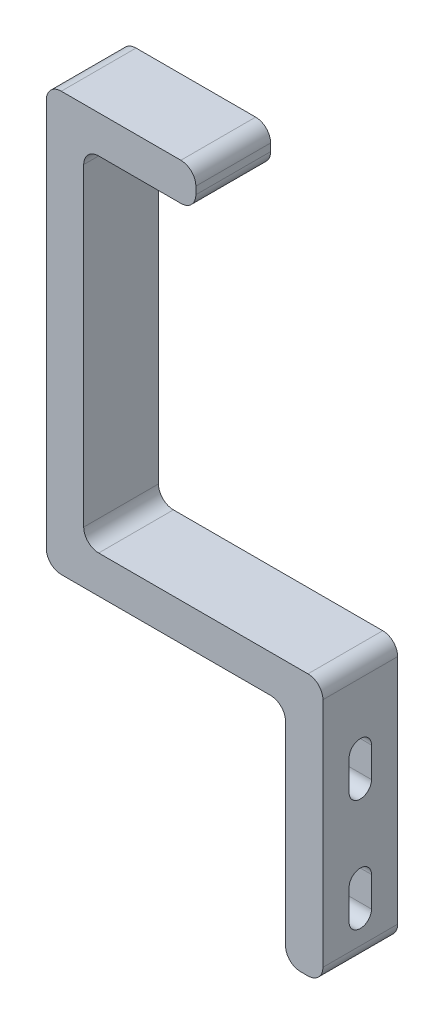
SolidWorks part; units mm, degrees
ref_plane "Front Plane" through (0, 0, 0) normal (0, 0, 1) x (1, 0, 0)
ref_plane "Top Plane" through (0, 0, 0) normal (0, 1, 0) x (1, 0, 0)
ref_plane "Right Plane" through (0, 0, 0) normal (1, 0, 0) x (0, 0, -1)
sketch "Sketch1" plane through (0, 0, 0) normal (0, 0, 1) x (1, 0, 0)
  line L0 (-2.5, 0) -> (-2.5, 30)
  line L5 (-2.5, 30) -> (-34.5, 30)
  line L6 (-34.5, 30) -> (-34.5, 86)
  line L7 (-34.5, 86) -> (-14.5, 86)
  line L8 (2.5, 0) -> (2.5, 35)
  line L9 (2.5, 35) -> (-29.5, 35)
  line L10 (-29.5, 35) -> (-29.5, 81)
  line L11 (-29.5, 81) -> (-29.5, 81)
  line L13 (-2.5, 0) -> (2.5, 0)
  line L14 (-34.5, 86) -> (-29.5, 86) construction
  line L15 (-14.5, 86) -> (-14.5, 81)
  line L16 (-14.5, 81) -> (-29.5, 81)
  point P14 (0, 0)
  dimension "D1" = 5
  dimension "D2" = 30
  dimension "D3" = 46
  dimension "D4" = 32
  dimension "D5" = 15
  dimension "D6" = 5
extrude "Boss-Extrude1" add sketch "Sketch1" along normal blind 10 contours L16 L15 L7 L6 L5 L0 L13 L8 L9 L10 region at (-1.5638, 15, 0)
sketch "Sketch3" plane through (-2.5, 0, 0) normal (-1, 0, 0) x (0, 0, 1)
  line L0 (10, 30) -> (0, 0) construction
  line L1 (10, 0) -> (0, 30) construction
  line L2 (5, 15) -> (23.8434, 15) construction
  line L3 (5, 24.5) -> (5, 20.5) construction
  line L4 (6.5, 24.5) -> (6.5, 20.5)
  line L5 (3.5, 24.5) -> (3.5, 20.5)
  line L6 (5, 5.5) -> (5, 9.5) construction
  line L7 (6.5, 5.5) -> (6.5, 9.5)
  line L8 (3.5, 5.5) -> (3.5, 9.5)
  arc A2 (6.5, 24.5) -> (3.5, 24.5) centre (5, 24.5) ccw
  arc A3 (3.5, 20.5) -> (6.5, 20.5) centre (5, 20.5) ccw
  arc A4 (6.5, 5.5) -> (3.5, 5.5) centre (5, 5.5) cw
  arc A5 (3.5, 9.5) -> (6.5, 9.5) centre (5, 9.5) cw
  point P12 (5, 22.5)
  point P19 (5, 7.5)
  dimension "D1" = 3
  dimension "D2" = 4
  dimension "D3" = 15
extrude "Cut-Extrude1" cut sketch "Sketch3" against normal through all both and the other way through all
chamfer "Chamfer2" distance 2 angle 30 8 edges at (-2.5, 7.5, 6.5) (-2.5, 11, 5) (-2.5, 4, 5) (-2.5, 7.5, 3.5) (-2.5, 22.5, 6.5) (-2.5, 26, 5) (-2.5, 19, 5) (-2.5, 22.5, 3.5) first distance on face at (-2.5, 22.5, 5)
fillet "Fillet1" radius 2 10 edges at (-14.5, 81, 5) (-14.5, 86, 5) (-34.5, 86, 5) (-34.5, 30, 5) (-2.5, 30, 5) (-2.5, 0, 5) (2.5, 0, 5) (2.5, 35, 5) (-29.5, 81, 5) (-29.5, 35, 5)
